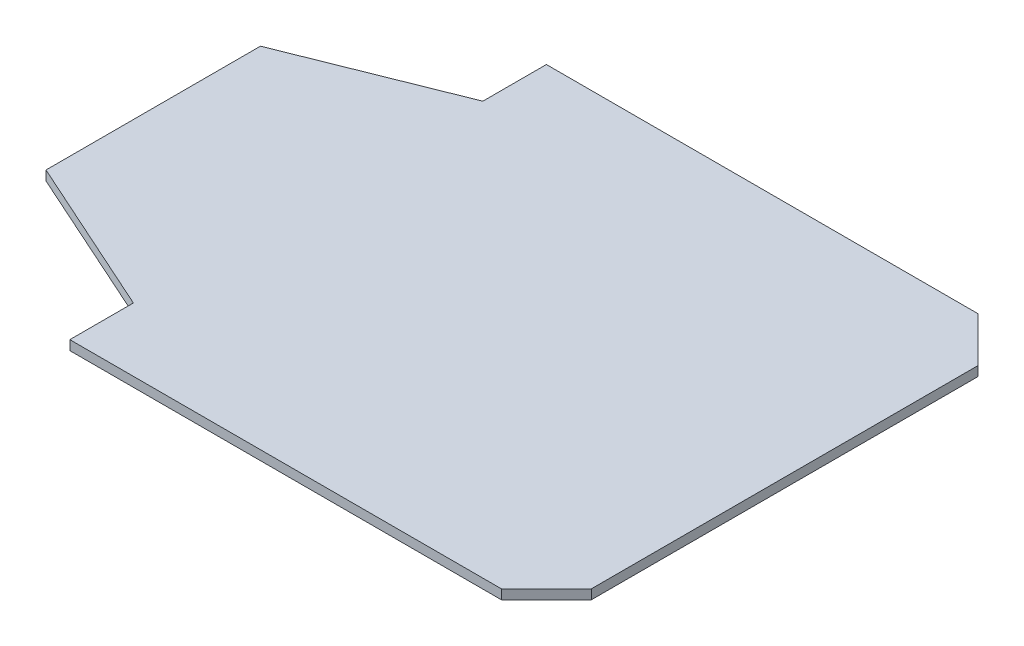
SolidWorks part; units mm, degrees
material "Acrylic (Medium-high impact)"
ref_plane "Front Plane" through (0, 0, 0) normal (0, 0, 1) x (1, 0, 0)
ref_plane "Top Plane" through (0, 0, 0) normal (0, 1, 0) x (1, 0, 0)
ref_plane "Right Plane" through (0, 0, 0) normal (1, 0, 0) x (0, 0, -1)
sketch "Sketch1" plane through (0, 0, 0) normal (0, 1, 0) x (1, 0, 0)
  line L0 (-245.1836, 942.3231) -> (-245.1836, 742.3231)
  line L2 (-145.1836, 692.3231) -> (126.5321, 692.3231)
  line L3 (126.5321, 692.3231) -> (154.8164, 720.6074)
  line L4 (154.8164, 720.6074) -> (154.8164, 964.0388)
  line L6 (126.5321, 992.3231) -> (-145.1836, 992.3231)
  line L8 (126.5321, 992.3231) -> (154.8164, 964.0388)
  line L9 (-145.1836, 692.3231) -> (-245.1836, 692.3231)
  line L10 (-245.1836, 692.3231) -> (-245.1836, 742.3231)
  line L11 (-145.1836, 992.3231) -> (-245.1836, 992.3231)
  line L12 (-245.1836, 992.3231) -> (-245.1836, 942.3231)
  point P2 (154.8164, 842.3231)
  point P9 (-245.1836, 842.3231)
  dimension "D1" = 300
  dimension "D2" = 400
  dimension "D3" = 200
  dimension "D4" = 150
  dimension "D5" = 100
  dimension "D6" = 45
  dimension "D7" = 150
  dimension "D8" = 0
  dimension "D9" = 45
  dimension "D10" = 40
extrude "Boss-Extrude1" add sketch "Sketch1" along normal blind 6 contours L6 L11 L12 L0 L10 L9 L2 L3 L4 L8
sketch "Sketch2" plane through (0, 6, 0) normal (0, 1, 0) x (1, 0, 0)
  line L0 (-245.1836, 912.3231) -> (-145.1836, 952.3231)
  line L1 (-245.1836, 692.3231) -> (-245.1836, 992.3231) construction
  line L2 (-145.1836, 952.3231) -> (-145.1836, 992.3231)
  line L3 (126.5321, 992.3231) -> (-245.1836, 992.3231) construction
  line L4 (-145.1836, 992.3231) -> (-245.1836, 992.3231)
  line L5 (-245.1836, 992.3231) -> (-245.1836, 912.3231)
  line L6 (-245.1836, 777.3231) -> (-145.1836, 732.3231)
  line L7 (-145.1836, 732.3231) -> (-145.1836, 692.3231)
  line L8 (-245.1836, 692.3231) -> (126.5321, 692.3231) construction
  line L9 (-145.1836, 692.3231) -> (-245.1836, 692.3231)
  line L10 (-245.1836, 692.3231) -> (-245.1836, 777.3231)
  point P19 (-145.1836, 952.3231)
  point P20 (-145.1836, 732.3231)
  dimension "D1" = 40
  dimension "D2" = 45
extrude "Cut-Extrude1" cut sketch "Sketch2" against normal blind 10
